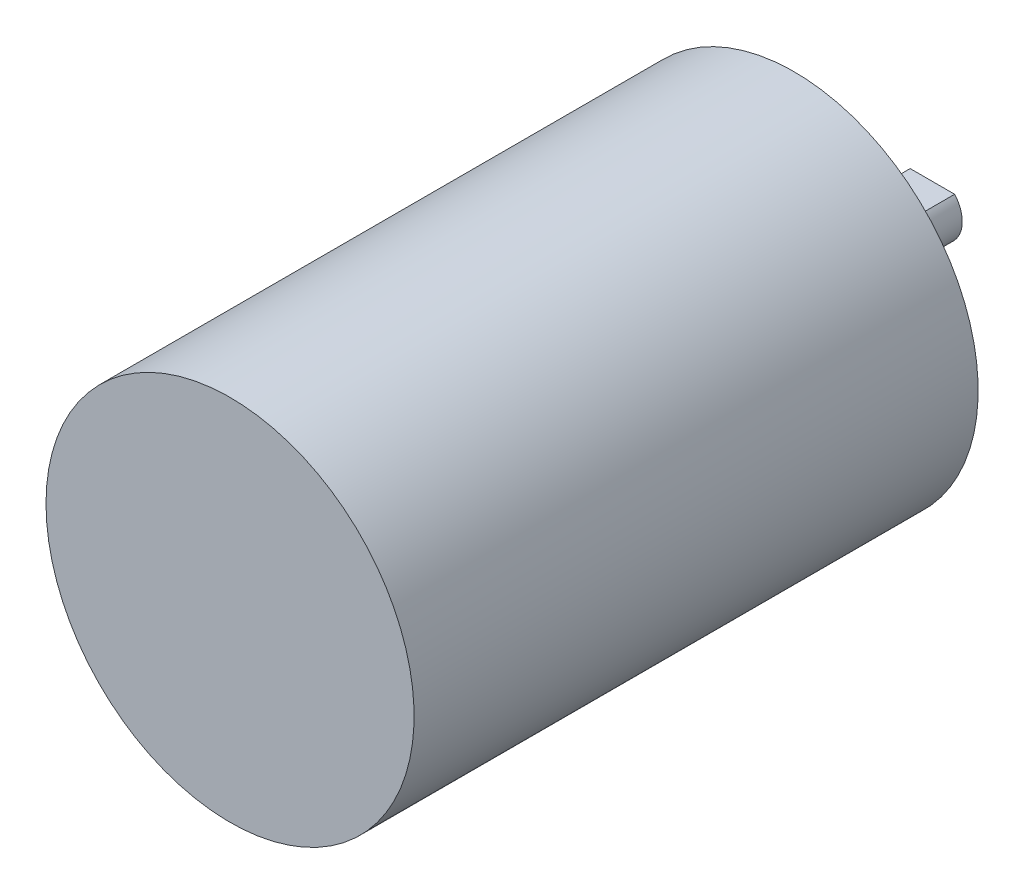
SolidWorks part; units mm, degrees
ref_plane "Front Plane" through (0, 0, 0) normal (0, 0, 1) x (1, 0, 0)
ref_plane "Top Plane" through (0, 0, 0) normal (0, 1, 0) x (1, 0, 0)
ref_plane "Right Plane" through (0, 0, 0) normal (1, 0, 0) x (0, 0, -1)
sketch "Sketch1" plane through (0, 0, 0) normal (0, 0, 1) x (1, 0, 0)
  circle A0 centre (0, 0) radius 18.5
  dimension "D1" = 37
extrude "Boss-Extrude1" add sketch "Sketch1" along normal blind 56.7
sketch "Sketch2" plane through (0, 0, 56.7) normal (0, 0, 1) x (1, 0, 0)
  point P0 (0, 0)
sketch "Sketch3" plane through (0, 0, 0) normal (0, 0, 1) x (1, 0, 0)
  circle A0 centre (0, 0) radius 6
  dimension "D1" = 12
extrude "Boss-Extrude2" add sketch "Sketch3" against normal blind 3.5
sketch "Sketch4" plane through (0, 0, -3.5) normal (0, 0, -1) x (-1, 0, 0)
  circle A0 centre (0, 0) radius 3
  dimension "D1" = 6
extrude "Boss-Extrude3" add sketch "Sketch4" along normal blind 10.4
sketch "Sketch5" plane through (0, 0, -13.9) normal (0, 0, -1) x (-1, 0, 0)
  line L0 (-2.2361, 2) -> (2.2361, 2)
  line L1 (0, 2) -> (0, 3) construction
  circle A0 centre (0, 0) radius 3 construction
  arc A1 (2.2361, 2) -> (-2.2361, 2) centre (0, 0) ccw
  dimension "D1" = 1
extrude "Cut-Extrude1" cut sketch "Sketch5" against normal blind 8
equation "\"MotorDIA\"= 37' Motor Diameter"
equation "\"SyringeDIA\"= 31.4'60ml Syringe Diameter"
equation "\"MotorShaftDIA\"= 6'Motor Shaft Dia"
equation "\"MotorKeyway\"= 1'Motor Shaft Keyway Depth"
equation "\"MotorLength\"= 56.7'Motor Length Excluding Shaft"
equation "\"SyringeLength\"= 117.3'60ml Syringe Length Excluding Nozzle"
equation "\"3Dtol\"= .5'Sizing Tolerance for 3D printed parts"
equation "\"ChamberDIA\"= 100 - 4'Buoyancy Chamber inner Diameter"
equation "\"ChamberThk\"= 2mm'Buoyancy Chamber Wall Thickness"
equation "\"BearingOD\"= 10"
equation "\"BearingID\"= 4"
equation "\"Bearingwidth\"= 4"
equation "\"ShaftDIA\"= 4"
equation "\"D1@Sketch1\"=\"MotorDIA\""
equation "\"D1@Boss-Extrude1\"=\"MotorLength\""
